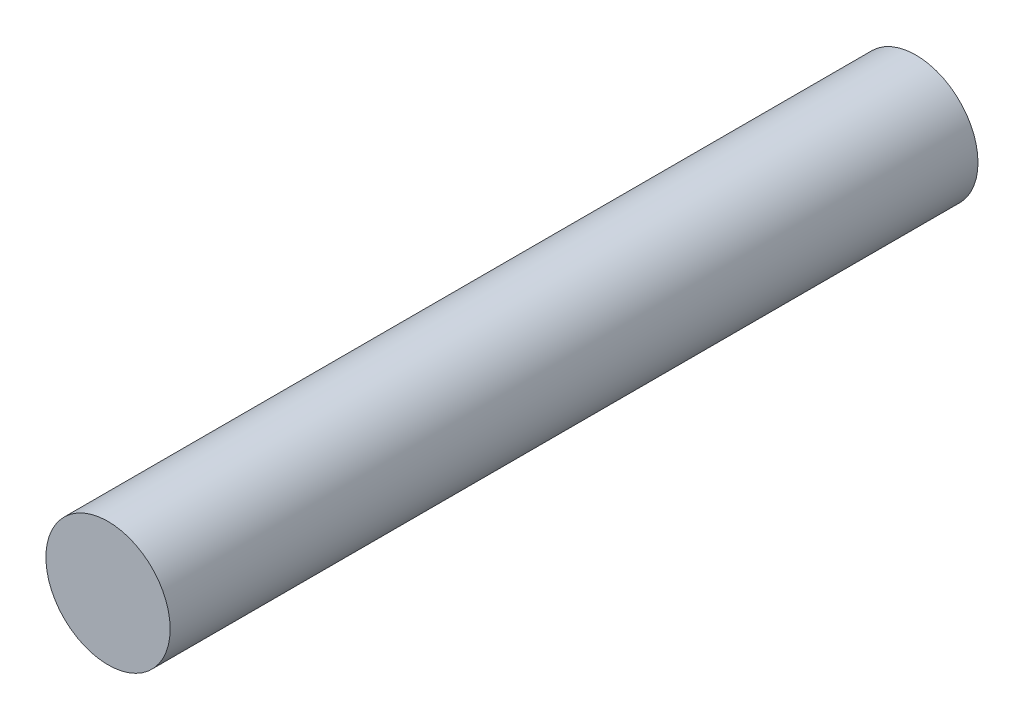
SolidWorks part; units mm, degrees
material "6061-T6 (SS)"
ref_plane "Front" through (0, 0, 0) normal (0, 0, 1) x (1, 0, 0)
ref_plane "Top" through (0, 0, 0) normal (0, 1, 0) x (1, 0, 0)
ref_plane "Right" through (0, 0, 0) normal (1, 0, 0) x (0, 0, -1)
sketch "Sketch1" plane through (0, 0, 0) normal (0, 0, 1) x (1, 0, 0)
  circle A0 centre (0, 0) radius 3.175
  point P1 (0, 0)
  dimension "D1" = 6.35
extrude "Boss-Extrude1" add sketch "Sketch1" along normal blind 41.275
